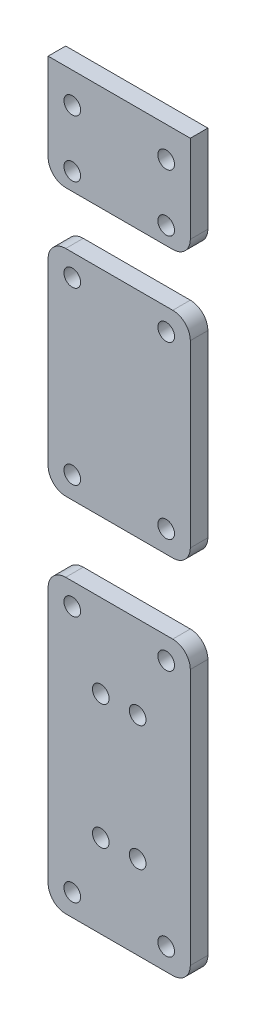
SolidWorks part; units mm, degrees
ref_plane "Front Plane" through (0, 0, 0) normal (0, 0, 1) x (1, 0, 0)
ref_plane "Top Plane" through (0, 0, 0) normal (0, 1, 0) x (1, 0, 0)
ref_plane "Right Plane" through (0, 0, 0) normal (1, 0, 0) x (0, 0, -1)
sketch "Sketch1" plane through (0, 0, 0) normal (0, 0, 1) x (1, 0, 0)
  line L0 (16.2, 1.5) -> (16.2, 14) construction
  line L1 (16.2, 109.64) -> (0, 109.64)
  line L2 (0, 109.64) -> (0, 99.66)
  line L3 (0, 1.5) -> (16.2, 1.5) construction
  line L4 (14.2, 59.21) -> (12.2, 59.21)
  line L5 (0, 14) -> (4, 14) construction
  line L6 (2, 26) -> (4, 26)
  line L7 (2, 91.66) -> (2.75, 91.66)
  line L8 (2, 67.21) -> (4, 67.21)
  line L9 (8.1, 109.64) -> (8.1, 97.66) construction
  line L10 (0, 14) -> (0, 1.5) construction
  line L11 (2, 97.66) -> (2.75, 97.66)
  line L12 (16.2, 28) -> (16.2, 57.21)
  line L13 (16.2, 99.66) -> (16.2, 109.64)
  line L14 (0, 89.66) -> (0, 69.21)
  line L15 (0, 57.21) -> (0, 28)
  line L16 (16.2, 69.21) -> (16.2, 89.66)
  line L17 (6, 14) -> (6, 26)
  line L18 (4, 59.21) -> (4, 67.21)
  line L19 (4, 14) -> (4, 26)
  line L20 (6, 59.21) -> (6, 67.21)
  line L21 (4, 91.66) -> (4, 97.66)
  line L22 (2.75, 97.66) -> (2.75, 91.66)
  line L23 (10.2, 14) -> (10.2, 26)
  line L24 (12.2, 14) -> (12.2, 26)
  line L25 (10.2, 59.21) -> (10.2, 67.21)
  line L26 (12.2, 59.21) -> (12.2, 67.21)
  line L27 (13.45, 91.66) -> (13.45, 97.66)
  line L28 (12.2, 91.66) -> (12.2, 97.66)
  line L29 (4, 97.66) -> (12.2, 97.66)
  line L30 (4, 91.66) -> (12.2, 91.66)
  line L31 (13.45, 91.66) -> (14.2, 91.66)
  line L32 (13.45, 97.66) -> (14.2, 97.66)
  line L33 (6, 67.21) -> (10.2, 67.21)
  line L34 (12.2, 67.21) -> (14.2, 67.21)
  line L35 (10.2, 59.21) -> (6, 59.21)
  line L36 (4, 59.21) -> (2, 59.21)
  line L37 (6, 14) -> (10.2, 14) construction
  line L38 (6, 26) -> (10.2, 26)
  line L39 (12.2, 26) -> (14.2, 26)
  line L40 (12.2, 14) -> (16.2, 14) construction
  line L41 (12.2, 14) -> (10.2, 14)
  line L42 (6, 14) -> (4, 14)
  circle A0 centre (13.45, 56.71) radius 0.95
  circle A1 centre (10.2, 49.71) radius 0.95
  circle A2 centre (13.45, 106.16) radius 0.95
  circle A3 centre (2.75, 99.66) radius 0.95
  circle A4 centre (6, 49.71) radius 0.95
  circle A5 centre (2.75, 28.5) radius 0.95
  circle A6 centre (2.75, 89.16) radius 0.95
  circle A7 centre (2.75, 56.71) radius 0.95
  circle A8 centre (13.45, 89.16) radius 0.95
  circle A9 centre (13.45, 99.66) radius 0.95
  arc A10 (16.2, 28) -> (14.2, 26) centre (14.2, 28) cw
  arc A11 (0, 28) -> (2, 26) centre (2, 28) ccw
  arc A12 (16.2, 57.21) -> (14.2, 59.21) centre (14.2, 57.21) ccw
  arc A13 (0, 57.21) -> (2, 59.21) centre (2, 57.21) cw
  arc A14 (16.2, 69.21) -> (14.2, 67.21) centre (14.2, 69.21) cw
  arc A15 (0, 69.21) -> (2, 67.21) centre (2, 69.21) ccw
  arc A16 (0, 89.66) -> (2, 91.66) centre (2, 89.66) cw
  arc A17 (16.2, 89.66) -> (14.2, 91.66) centre (14.2, 89.66) ccw
  arc A18 (16.2, 99.66) -> (14.2, 97.66) centre (14.2, 99.66) cw
  arc A19 (2, 97.66) -> (0, 99.66) centre (2, 99.66) cw
  circle A28 centre (13.45, 69.71) radius 0.95
  circle A29 centre (6, 35.5) radius 0.95
  circle A32 centre (2.75, 106.16) radius 0.95
  circle A33 centre (10.2, 35.5) radius 0.95
  circle A34 centre (2.75, 69.71) radius 0.95
  circle A35 centre (13.45, 28.5) radius 0.95
  circle A36 centre (2.85, 11.5) radius 0.95 construction
  circle A37 centre (13.35, 11.5) radius 0.95 construction
  circle A38 centre (13.35, 5.5) radius 0.95 construction
  circle A39 centre (2.85, 5.5) radius 0.95 construction
  point P71 (16.2, 26)
  point P74 (0, 26)
  point P91 (16.2, 59.21)
  point P94 (0, 59.21)
  point P97 (16.2, 67.21)
  point P100 (0, 67.21)
  point P103 (0, 91.66)
  point P106 (16.2, 91.66)
  point P109 (16.2, 97.66)
  point P112 (0, 97.66)
  dimension "D1" = 4
  dimension "D45" = 1.9
  dimension "D46" = 2
  dimension "D2" = 4
  dimension "D3" = 2.85
  dimension "D4" = 2.85
  dimension "D5" = 16.2
  dimension "D6" = 6
  dimension "D7" = 6
  dimension "D8" = 2.85
  dimension "D9" = 2.85
  dimension "D10" = 2.5
  dimension "D11" = 12
  dimension "D12" = 33.21
  dimension "D13" = 2.5
  dimension "D14" = 2.5
  dimension "D15" = 2.75
  dimension "D16" = 2.75
  dimension "D17" = 2.5
  dimension "D18" = 2.5
  dimension "D19" = 2.75
  dimension "D20" = 2.75
  dimension "D21" = 9.5
  dimension "D22" = 6
  dimension "D23" = 9.5
  dimension "D24" = 6
  dimension "D25" = 9.5
  dimension "D26" = 9.5
  dimension "D27" = 6
  dimension "D28" = 6
  dimension "D29" = 8
  dimension "D30" = 24.45
  dimension "D31" = 2.5
  dimension "D32" = 2.5
  dimension "D33" = 2.75
  dimension "D34" = 2.75
  dimension "D35" = 6
  dimension "D36" = 2.75
  dimension "D37" = 2
  dimension "D38" = 2.75
  dimension "D39" = 8.5
  dimension "D40" = 11.98
  dimension "D41" = 2.5
  dimension "D42" = 2.5
  dimension "D43" = 2.75
  dimension "D44" = 2.75
extrude "Boss-Extrude1" add sketch "Sketch1" along normal blind 2
sketch "Sketch2" plane through (0, 0, 0) normal (0, 0, -1) x (-1, 0, 0)
  line L0 (-13.45, 97.66) -> (-2.75, 97.66)
  line L1 (-2.75, 97.66) -> (-2.75, 91.66)
  line L2 (-2.75, 91.66) -> (-13.45, 91.66)
  line L3 (-13.45, 91.66) -> (-13.45, 97.66)
  line L4 (-12.2, 67.21) -> (-4, 67.21)
  line L5 (-4, 67.21) -> (-4, 59.21)
  line L6 (-4, 59.21) -> (-12.2, 59.21)
  line L7 (-12.2, 59.21) -> (-12.2, 67.21)
  line L8 (-12.2, 26) -> (-4, 26)
  line L9 (-4, 26) -> (-4, 14)
  line L10 (-4, 14) -> (-12.2, 14)
  line L11 (-12.2, 14) -> (-12.2, 26)
extrude "Cut-Extrude1" cut sketch "Sketch2" against normal up to surface (2 mm away) up to face at (3.7, 69.71, 2)
